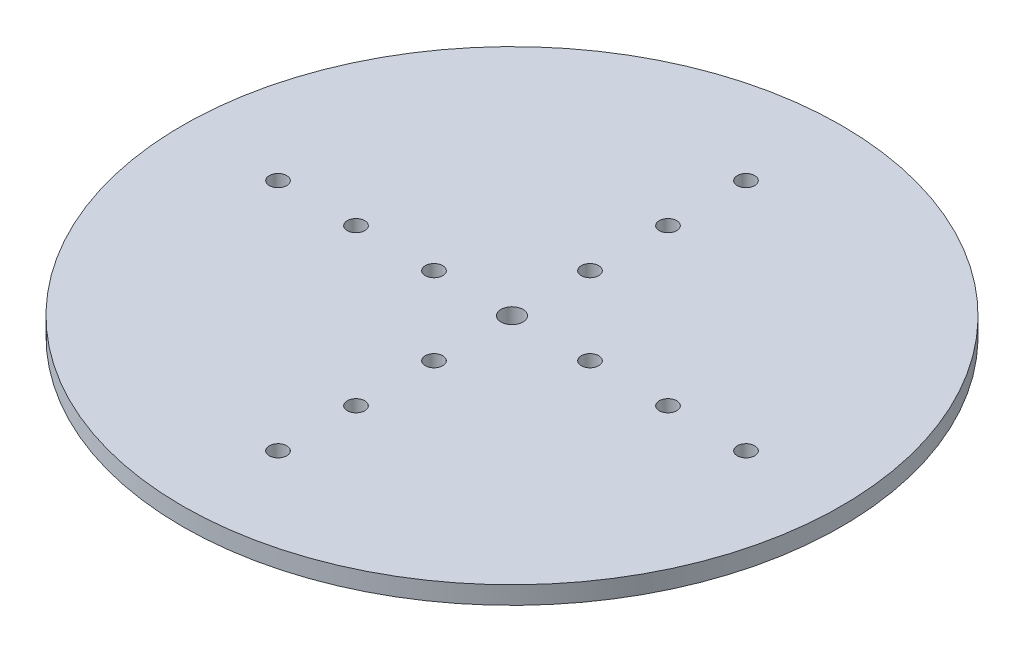
SolidWorks part; units mm, degrees
ref_plane "Alzado" through (0, 0, 0) normal (0, 0, 1) x (1, 0, 0)
ref_plane "Planta" through (0, 0, 0) normal (0, 1, 0) x (1, 0, 0)
ref_plane "Vista lateral" through (0, 0, 0) normal (1, 0, 0) x (0, 0, -1)
sketch "Croquis1" plane through (0, 0, 0) normal (0, 1, 0) x (1, 0, 0)
  circle A0 centre (0, 0) radius 120
  dimension "D1" = 240
extrude "Saliente-Extruir1" add sketch "Croquis1" along normal blind 6.5
sketch "Croquis2" plane through (0, 6.5, 0) normal (0, 1, 0) x (1, 0, 0)
  circle A0 centre (0, 0) radius 4
  dimension "D1" = 8
extrude "Cortar-Extruir1" cut sketch "Croquis2" against normal blind 6.5
sketch "Croquis3" plane through (0, 0, 0) normal (0, -1, 0) x (-1, 0, 0)
  line L0 (-25.225, 0) -> (-31.575, 0) construction
  line L1 (0, -120) -> (0, 120) construction
  line L2 (-53.625, 0) -> (-59.975, 0) construction
  line L3 (-82.025, 0) -> (-88.375, 0) construction
  line L4 (82.025, 0) -> (88.375, 0) construction
  line L5 (53.625, 0) -> (59.975, 0) construction
  line L6 (25.225, 0) -> (31.575, 0) construction
  line L7 (120, 0) -> (-120, 0) construction
  circle A0 centre (0, 0) radius 120 construction
  circle A1 centre (-28.4, 0) radius 3.175
  circle A2 centre (0, 0) radius 4 construction
  circle A3 centre (-56.8, 0) radius 3.175
  circle A4 centre (-85.2, 0) radius 3.175
  circle A5 centre (85.2, 0) radius 3.175
  circle A6 centre (56.8, 0) radius 3.175
  circle A7 centre (28.4, 0) radius 3.175
  circle A8 centre (0, -28.4) radius 3.175
  circle A9 centre (0, -56.8) radius 3.175
  circle A10 centre (0, -85.2) radius 3.175
  circle A11 centre (0, 85.2) radius 3.175
  circle A12 centre (0, 56.8) radius 3.175
  circle A13 centre (0, 28.4) radius 3.175
  dimension "D1" = 6.35
  dimension "D3" = 6.35
  dimension "D4" = 28.4
  dimension "D5" = 6.35
  dimension "D6" = 28.4
  dimension "D7" = 6.35
  dimension "D8" = 28.4
  dimension "D9" = 6.35
  dimension "D10" = 28.4
  dimension "D11" = 6.35
  dimension "D12" = 28.4
  dimension "D2" = 28.4
extrude "Cortar-Extruir2" cut sketch "Croquis3" against normal blind 6.5
